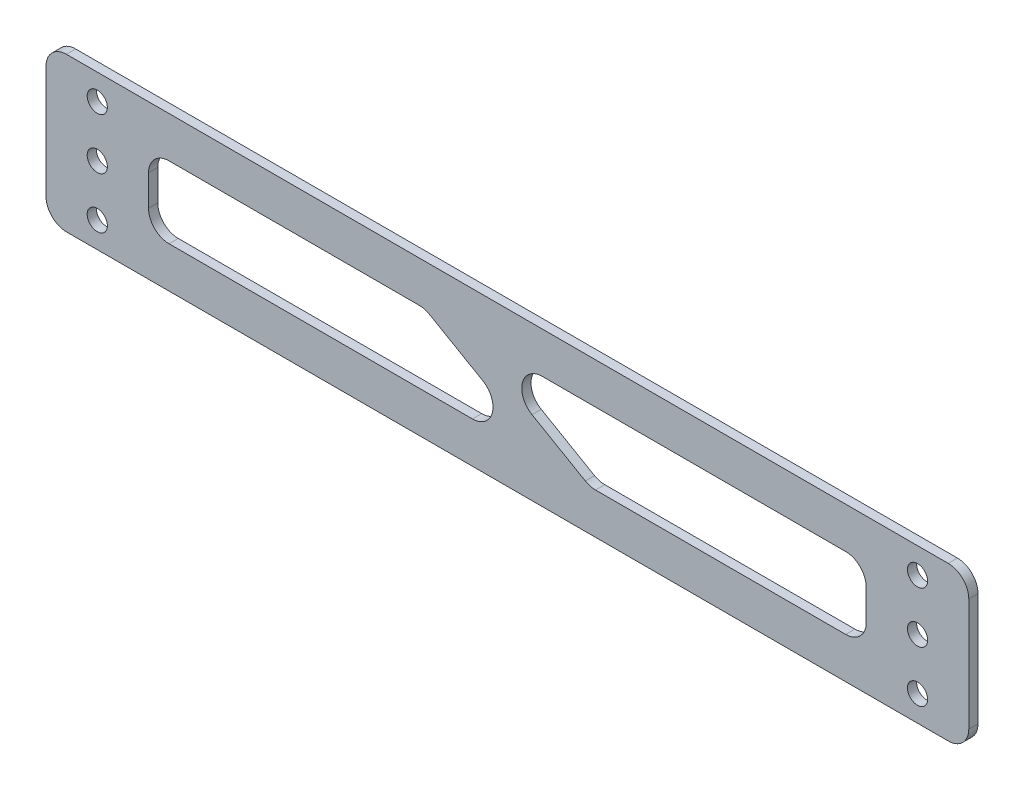
SolidWorks part; units mm, degrees
material "6061-T6 (SS)"
ref_plane "Front Plane" through (0, 0, 0) normal (0, 0, 1) x (1, 0, 0)
ref_plane "Top Plane" through (0, 0, 0) normal (0, 1, 0) x (1, 0, 0)
ref_plane "Right Plane" through (0, 0, 0) normal (1, 0, 0) x (0, 0, -1)
sketch "Sketch1" plane through (0, 0, 0) normal (0, 0, 1) x (1, 0, 0)
  line L1 (-12.7, 774.7) -> (49987.3, 774.7) construction
  line L2 (-7.62, 368.3) -> (210.82, 368.3) construction
  line L3 (-12.7, 1181.1) -> (-12.7, 368.3) construction
  line L4 (-7.62, 755.65) -> (210.82, 755.65)
  line L5 (-12.7, 760.73) -> (-12.7, 788.67)
  line L6 (-7.62, 793.75) -> (210.82, 793.75)
  line L7 (215.9, 760.73) -> (215.9, 788.67)
  line L8 (215.9, 1181.1) -> (215.9, 368.3) construction
  line L9 (17.78, 783.59) -> (79.7609, 783.59)
  line L10 (12.7, 1181.1) -> (12.7, 368.3) construction
  line L11 (190.5, 1181.1) -> (190.5, 368.3) construction
  line L12 (190.5, 778.51) -> (190.5, 770.89)
  line L13 (185.42, 765.81) -> (123.4391, 765.81)
  line L14 (12.7, 770.89) -> (12.7, 778.51)
  line L15 (82.3009, 782.9094) -> (95.4991, 775.2894)
  line L16 (107.7009, 774.1106) -> (120.8991, 766.4906)
  line L17 (81.1221, 783.59) -> (81.1221, -49216.41) construction
  line L18 (122.0779, 765.81) -> (122.0779, 50765.81) construction
  line L19 (101.6, 765.81) -> (101.6, 50765.81) construction
  line L20 (110.2409, 783.59) -> (185.42, 783.59)
  line L21 (92.9591, 765.81) -> (17.78, 765.81)
  arc A0 (210.82, 793.75) -> (215.9, 788.67) centre (210.82, 788.67) cw
  arc A1 (210.82, 755.65) -> (215.9, 760.73) centre (210.82, 760.73) ccw
  arc A2 (-12.7, 788.67) -> (-7.62, 793.75) centre (-7.62, 788.67) cw
  arc A3 (-7.62, 755.65) -> (-12.7, 760.73) centre (-7.62, 760.73) cw
  circle A4 centre (0, 762) radius 2.5
  circle A5 centre (0, 774.7) radius 2.5
  circle A6 centre (0, 787.4) radius 2.5
  circle A7 centre (203.2, 762) radius 2.5
  circle A8 centre (203.2, 774.7) radius 2.5
  circle A9 centre (203.2, 787.4) radius 2.5
  arc A10 (185.42, 783.59) -> (190.5, 778.51) centre (185.42, 778.51) cw
  arc A11 (190.5, 770.89) -> (185.42, 765.81) centre (185.42, 770.89) cw
  arc A12 (17.78, 765.81) -> (12.7, 770.89) centre (17.78, 770.89) cw
  arc A13 (17.78, 783.59) -> (12.7, 778.51) centre (17.78, 778.51) ccw
  arc A14 (120.8991, 766.4906) -> (123.4391, 765.81) centre (123.4391, 770.89) ccw
  arc A15 (107.7009, 774.1106) -> (110.2409, 783.59) centre (110.2409, 778.51) cw
  arc A16 (82.3009, 782.9094) -> (79.7609, 783.59) centre (79.7609, 778.51) ccw
  arc A17 (95.4991, 775.2894) -> (92.9591, 765.81) centre (92.9591, 770.89) cw
  point P14 (215.9, 793.75)
  point P17 (215.9, 755.65)
  point P22 (-12.7, 755.65)
  point P55 (190.5, 783.59)
  point P58 (190.5, 765.81)
  point P61 (12.7, 765.81)
  point P64 (12.7, 783.59)
  point P73 (122.0779, 765.81)
  point P76 (91.2821, 783.59)
  point P79 (81.1221, 783.59)
  point P82 (111.9179, 765.81)
  dimension "D4" = 5.08
  dimension "D7" = 5.08
  dimension "D12" = 5.08
  dimension "D1" = 406.4
  dimension "D2" = 38.1
  dimension "D3" = 19.05
  dimension "D5" = 10.16
  dimension "D6" = 10.16
  dimension "D8" = 5.08
  dimension "D9" = 30
  dimension "D10" = 20.4779
  dimension "D11" = 88.9
extrude "Boss-Extrude1" add sketch "Sketch1" along normal blind 2.286
